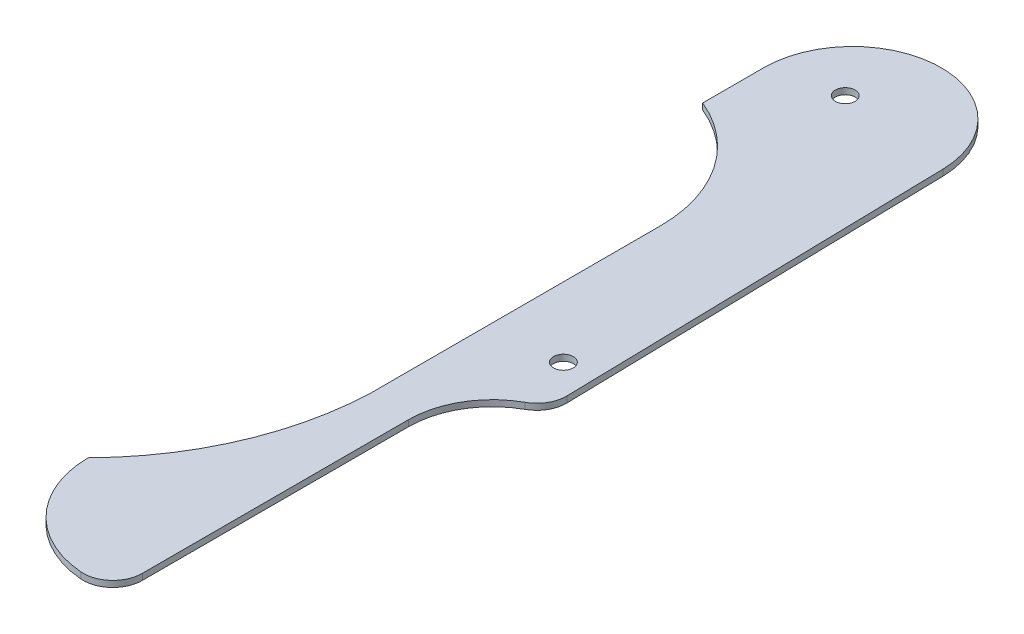
SolidWorks part; units mm, degrees
ref_plane "Płaszczyzna przednia" through (0, 0, 0) normal (0, 0, 1) x (1, 0, 0)
ref_plane "Płaszczyzna górna" through (0, 0, 0) normal (0, 1, 0) x (1, 0, 0)
ref_plane "Płaszczyzna prawa" through (0, 0, 0) normal (1, 0, 0) x (0, 0, -1)
sketch "Sketch1" plane through (0, 0, 0) normal (0, 1, 0) x (1, 0, 0)
  line L0 (0, -96.2847) -> (0, -45.5843) construction
  line L1 (8.9979, 2.4233) -> (9.8488, -36.5767)
  line L4 (-0.35, -44.1605) -> (-0.35, -16.9105)
  line L6 (-9, 2.227) -> (-9, -3.973)
  line L7 (3.9, -46.714) -> (3.9, -73.714)
  arc A0 (-9, 2.227) -> (8.9979, 2.4233) centre (0, 2.227) cw
  arc A1 (9.8488, -36.5767) -> (8.2975, -39.2696) centre (6.8496, -36.6421) cw
  arc A2 (8.2975, -39.2696) -> (3.9, -46.714) centre (12.4, -46.714) ccw
  arc A5 (-0.35, -16.9105) -> (-9, -3.973) centre (-14.35, -16.9105) ccw
  arc A7 (3.9, -73.714) -> (0.6601, -76.7044) centre (0.9, -73.714) cw
  arc A9 (0.6601, -76.7044) -> (-9, -66.3092) centre (1.4998, -66.238) cw
  arc A10 (-0.35, -44.1605) -> (-9, -66.3092) centre (-30.3315, -45.2149) cw
  circle A11 centre (-2.41, 3.897) radius 1
  circle A12 centre (6.7124, -33.8124) radius 1
  dimension "D1" = 9
  dimension "D3" = 3
  dimension "D4" = 8.5
  dimension "D5" = 3.9
  dimension "D6" = 3
  dimension "D7" = 10.5
  dimension "D8" = 30
  dimension "D10" = 14
  dimension "D14" = 27
  dimension "D2" = 39
  dimension "D9" = 27.25
  dimension "D11" = 6.2
  dimension "D12" = 0.7
  dimension "D13" = 1.25
extrude "Boss-Extrude1" add sketch "Sketch1" along normal blind 0.625
